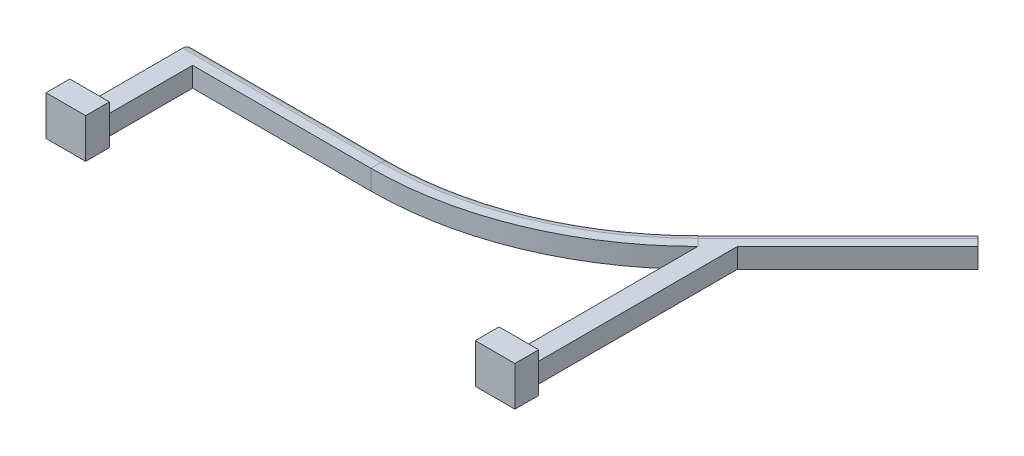
SolidWorks part; units mm, degrees
ref_plane "Front" through (0, 0, 0) normal (0, 0, 1) x (1, 0, 0)
ref_plane "Top" through (0, 0, 0) normal (0, 1, 0) x (1, 0, 0)
ref_plane "Right" through (0, 0, 0) normal (1, 0, 0) x (0, 0, -1)
sketch "Sketch1" plane through (0, 0, 0) normal (0, 1, 0) x (1, 0, 0)
  line L0 (0, 0) -> (50, 0)
  line L1 (106.5685, 23.4315) -> (141.9239, 58.7868)
  arc A0 (50, 0) -> (106.5685, 23.4315) centre (50, 80) ccw
  point P4 (0, 0)
  point P7 (0, 0)
  point P8 (0, 0)
  dimension "D2" = 80
  dimension "D1" = 45
  dimension "D3" = 50
  dimension "D4" = 50
sketch "Sketch2" plane through (0, 0, 0) normal (1, 0, 0) x (0, 0, -1)
  line L1 (-2.5, 2.5) -> (2.5, 2.5)
  line L2 (-2.5, 2.5) -> (-2.5, -2.5)
  line L3 (-2.5, -2.5) -> (2.5, -2.5)
  line L4 (2.5, 2.5) -> (2.5, -2.5)
  point P4 (0, 2.5)
  point P6 (-2.5, 0)
  dimension "D1" = 5
sweep "Sweep3" add profiles "Sketch2" path "Sketch1"
fillet "Fillet1" radius 2.5 6 edges at (122.4784, -2.5, -42.8769) (79.658, -2.5, -8.3993) (122.4784, 2.5, -42.8769) (79.658, 2.5, -8.3993) (25, -2.5, -2.5) (25, 2.5, -2.5)
sketch "Sketch3" plane through (0, 0, 0) normal (0, 1, 0) x (1, 0, 0)
  line L0 (0, -2.5) -> (0, -32)
  line L1 (0, -32) -> (5, -32)
  line L2 (5, -32) -> (5, -2.5)
  line L3 (0, -2.5) -> (50, -2.5) construction
  line L4 (5, -2.5) -> (0, -2.5)
  line L5 (0, 2.5) -> (50, 2.5) construction
  line L6 (108.3363, 21.6637) -> (113.3363, 26.6637)
  line L7 (108.3363, 21.6637) -> (143.6916, 57.019) construction
  line L8 (113.3363, 26.6637) -> (113.3363, -32)
  line L9 (113.3363, -32) -> (108.3363, -32)
  line L10 (108.3363, -32) -> (108.3363, 21.6637)
  dimension "D1" = 34.5
  dimension "D2" = 5
  dimension "D3" = 5
extrude "Boss-Extrude1" add sketch "Sketch3" along normal mid plane 5
sketch "Sketch4" plane through (0, 0, 32) normal (0, 0, 1) x (1, 0, 0)
  line L0 (0, -2.5) -> (5, -2.5) construction
  line L1 (-2.5, 7.5) -> (7.5, 7.5)
  line L2 (-2.5, 7.5) -> (-2.5, -2.5)
  line L3 (-2.5, -2.5) -> (7.5, -2.5)
  line L4 (7.5, 7.5) -> (7.5, -2.5)
  line L5 (105.8363, 7.5) -> (115.8363, 7.5)
  line L6 (105.8363, 7.5) -> (105.8363, -2.5)
  line L7 (105.8363, -2.5) -> (115.8363, -2.5)
  line L8 (115.8363, 7.5) -> (115.8363, -2.5)
  line L9 (0, 2.5) -> (5, 2.5) construction
  line L10 (108.3363, -2.5) -> (113.3363, -2.5) construction
  line L11 (108.3363, 2.5) -> (113.3363, 2.5) construction
  point P10 (2.5, -2.5)
  point P13 (2.5, 2.5)
  point P16 (110.8363, 7.5)
  point P19 (110.8363, 2.5)
  dimension "D1" = 10
  dimension "D2" = 10
  dimension "D3" = 10
  dimension "D4" = 10
extrude "Boss-Extrude2" add sketch "Sketch4" against normal blind 6
